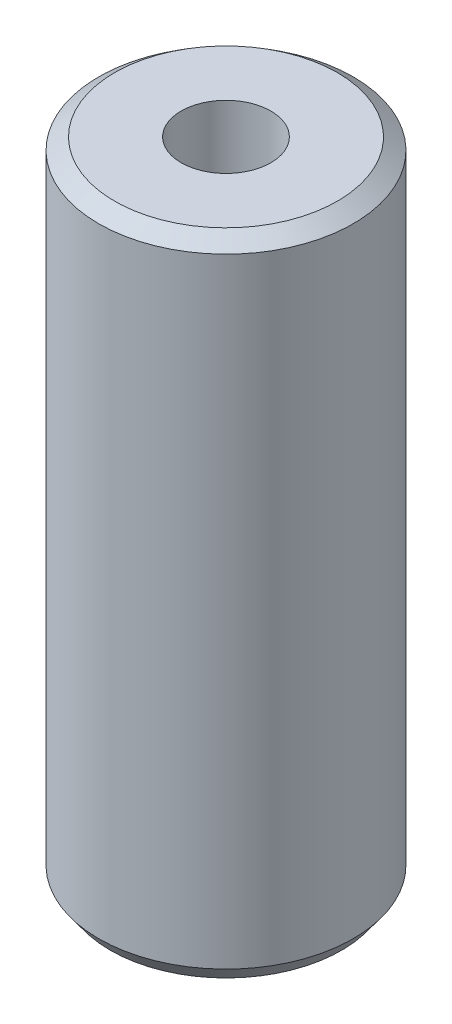
SolidWorks part; units mm, degrees
ref_plane "Front Plane" through (0, 0, 0) normal (0, 0, 1) x (1, 0, 0)
ref_plane "Top Plane" through (0, 0, 0) normal (0, 1, 0) x (1, 0, 0)
ref_plane "Right Plane" through (0, 0, 0) normal (1, 0, 0) x (0, 0, -1)
sketch "Sketch1" plane through (0, 0, 0) normal (0, 1, 0) x (1, 0, 0)
  circle A0 centre (0, 0) radius 42.5
  dimension "SHAFT_OD" = 85
extrude "Boss-Extrude1" add sketch "Sketch1" along normal blind 215.9369
sketch "Sketch2" plane through (0, 0, 0) normal (0, 1, 0) x (1, 0, 0)
  circle A0 centre (0, 0) radius 14.9753
  dimension "BORE_D" = 29.9506
extrude "Cut-Extrude1" cut sketch "Sketch2" along normal through all
chamfer "Chamfer1" distance 3.8752 angle 53.846 2 edges at (0, 215.9369, 42.5) (0, 0, 42.5) first distance on face at (0, 215.9369, 42.5) first distance on face at (0, 0, 14.9753)
